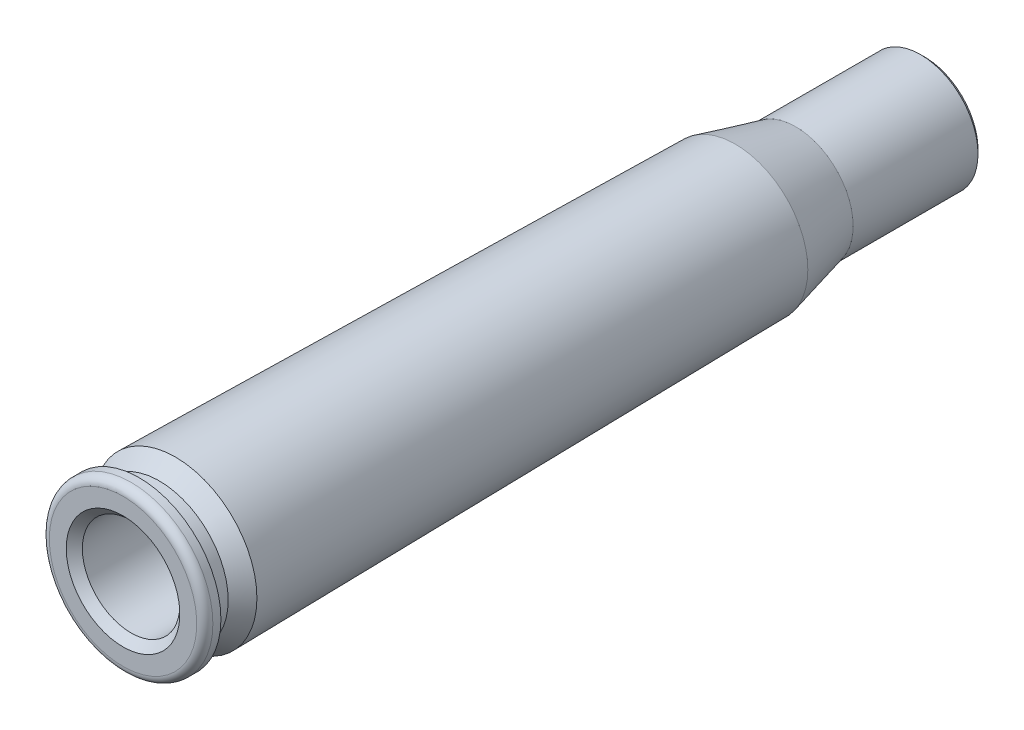
SolidWorks part; units mm, degrees
ref_plane "정면" through (0, 0, 0) normal (0, 0, 1) x (1, 0, 0)
ref_plane "윗면" through (0, 0, 0) normal (0, 1, 0) x (1, 0, 0)
ref_plane "우측면" through (0, 0, 0) normal (1, 0, 0) x (0, 0, -1)
sketch "스케치2" plane through (0, 0, 0) normal (1, 0, 0) x (0, 0, -1)
  line L0 (0, 0) -> (99.5, 0) construction
  line L1 (83.5, -7.125) -> (99.5, -7.125)
  line L2 (99.5, -7.125) -> (99.5, 0)
  line L3 (83.5, -7.125) -> (76, -9)
  line L4 (76, -9) -> (4.5, -10.15)
  line L5 (4.5, -10.15) -> (4.5, -8.55)
  line L6 (4.5, -8.55) -> (2, -8.55)
  line L7 (2, -8.55) -> (2, -10.15)
  line L8 (2, -10.15) -> (0, -10.15)
  line L9 (0, -10.15) -> (0, -6.05)
  line L10 (2, -10.15) -> (4.5, -10.15) construction
  line L11 (99.5, -6.05) -> (83.5, -6.05)
  line L12 (83.5, -6.05) -> (0, -6.05)
  line L15 (83.5, -6.05) -> (83.5, -7.125) construction
  line L16 (0, 0) -> (0, -6.05) construction
  dimension "D2" = 99.5
  dimension "D3" = 20.3
  dimension "D4" = 14.25
  dimension "D5" = 7.5
  dimension "D6" = 16
  dimension "D7" = 2
  dimension "D8" = 2.5
  dimension "D9" = 17.1
  dimension "D10" = 18
  dimension "D11" = 12.1
revolve "회전1" add sketch "스케치2" angle 360 about L0 region at (0, -7.7178, -41.6754)
chamfer "모따기1" distance 2 distance2 1.6 1 edges at (10.15, 0, -4.5) first distance on face at (10.15, 0, -4.5)
fillet "필렛1" radius 1 1 edges at (10.15, 0, 0)
chamfer "모따기2" distance 0.5 angle 45 1 edges at (7.125, 0, -99.5)
chamfer "모따기3" distance 1 angle 45 1 edges at (6.05, 0, 0)
